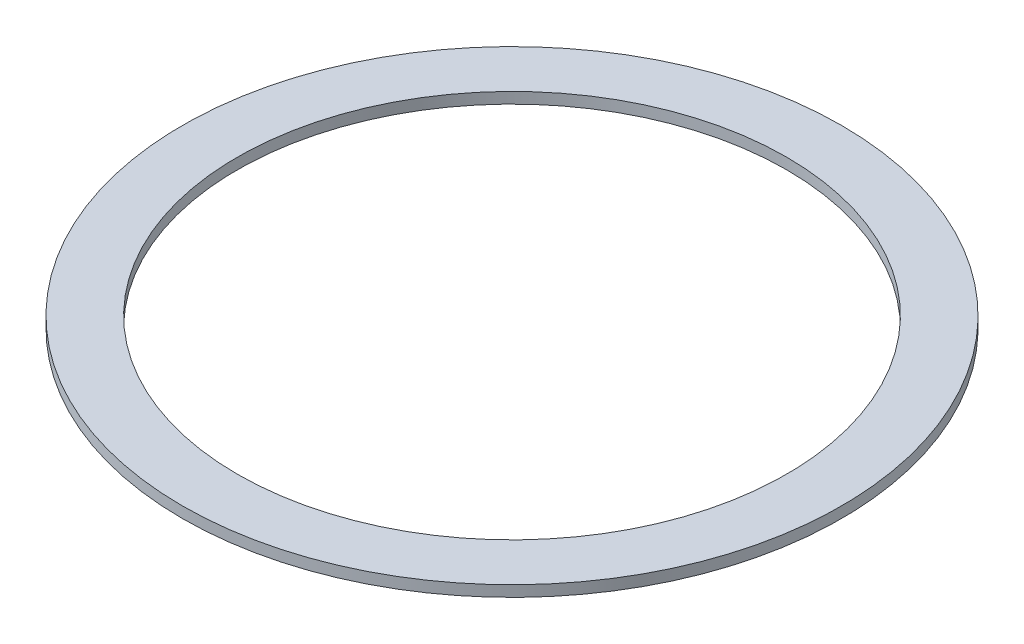
SolidWorks part; units mm, degrees
material "Медь"
ref_plane "Спереди" through (0, 0, 0) normal (0, 0, 1) x (1, 0, 0)
ref_plane "Сверху" through (0, 0, 0) normal (0, 1, 0) x (1, 0, 0)
ref_plane "Справа" through (0, 0, 0) normal (1, 0, 0) x (0, 0, -1)
sketch "Эскиз1" plane through (0, 0, 0) normal (0, 0, 1) x (1, 0, 0)
  line L0 (0, 131.0345) -> (0, -118.2266) construction
  line L1 (0, 0) -> (50, 0) construction
  line L3 (50, 1) -> (60, 1)
  line L4 (50, 1) -> (50, -1)
  line L5 (50, -1) -> (60, -1)
  line L6 (60, 1) -> (60, -1)
  point P9 (0, 0)
  dimension "D1" = 100
  dimension "D2" = 120
  dimension "D3" = 2
revolve "Повернуть1" add sketch "Эскиз1" angle 360 about L0
ref_axis "Ось1" through (0, 0, 0) along (0, 1, 0)
